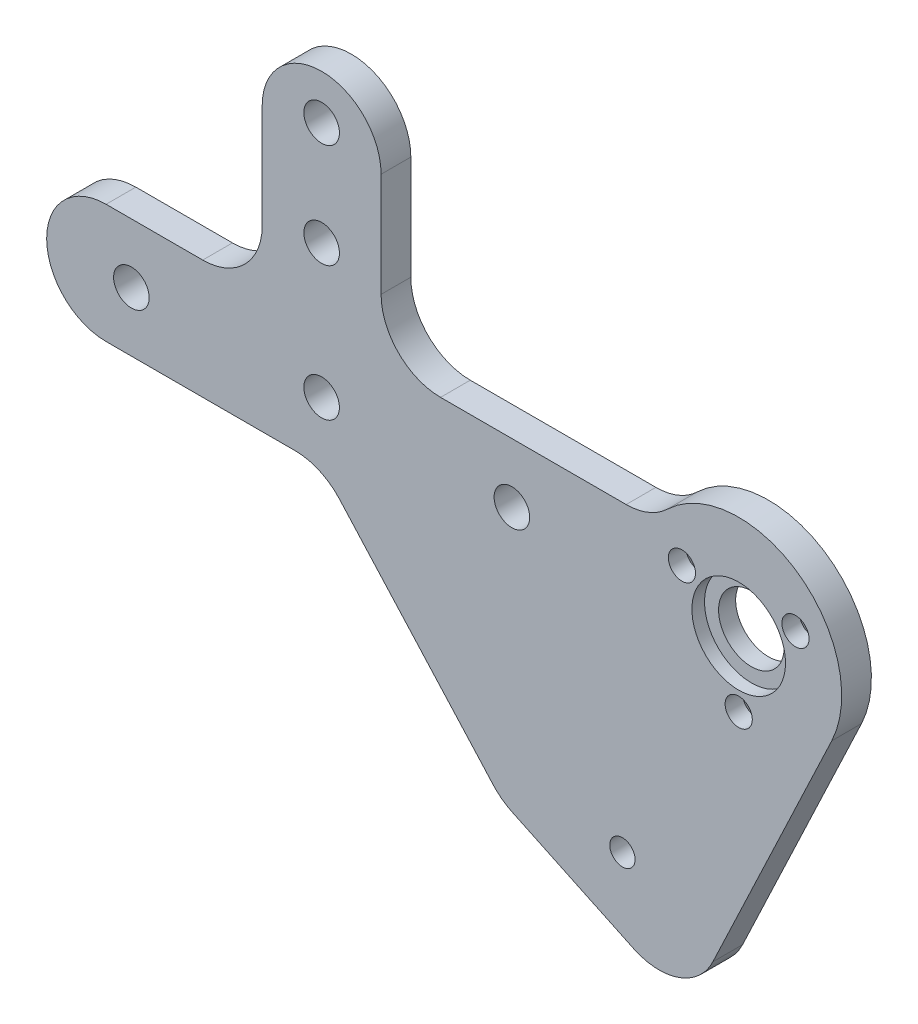
SolidWorks part; units mm, degrees
material "6061 Alloy"
ref_plane "Front Plane" through (0, 0, 0) normal (0, 0, 1) x (1, 0, 0)
ref_plane "Top Plane" through (0, 0, 0) normal (0, 1, 0) x (1, 0, 0)
ref_plane "Right Plane" through (0, 0, 0) normal (1, 0, 0) x (0, 0, -1)
sketch "Sketch1" plane through (0, 0, 0) normal (0, 0, 1) x (1, 0, 0)
  line L0 (0, 0) -> (0, 87.4403) construction
  line L1 (0, 0) -> (31.5741, 100.1403) construction
  line L2 (0, 0) -> (-31.5741, 100.1403) construction
  line L3 (-29.3687, 87.4403) -> (-29.3688, 100.1403)
  line L4 (29.3687, 100.1403) -> (35.4318, 100.1403)
  line L5 (31.5741, 100.1403) -> (-31.5741, 100.1403) construction
  line L6 (29.3687, 100.1403) -> (-29.3688, 100.1403)
  line L7 (0, 0) -> (38.5474, 81.3271) construction
  line L10 (-29.3687, 87.4403) -> (29.3687, 87.4403)
  line L12 (54.4836, 89.2666) -> (39.0647, 56.7358)
  line L13 (34.6037, 98.6893) -> (19.1847, 66.1585)
  line L14 (39.0647, 56.7358) -> (19.1847, 66.1585)
  line L17 (19.1847, 66.1585) -> (0, 87.4403)
  line L19 (0, 100.1403) -> (0, 123.9528) construction
  line L21 (6.35, 117.6028) -> (6.35, 100.1403)
  line L22 (-6.35, 117.6028) -> (-6.35, 100.1403)
  circle A0 centre (0, 0) radius 90 construction
  circle A1 centre (0, 0) radius 105 construction
  arc A2 (54.4836, 89.2666) -> (34.6037, 98.6893) centre (44.5437, 93.978) ccw
  circle A4 centre (44.5437, 93.978) radius 5
  circle A6 centre (0, 117.6028) radius 6.35
  circle A7 centre (44.5437, 93.978) radius 3.5
  point P14 (0, 100.1403)
  dimension "D1" = 17.5
  dimension "D3" = 25.36
  dimension "D6" = 180
  dimension "D4" = 23.8125
  dimension "D7" = 210
  dimension "D8" = 12.7
  dimension "D9" = 22
  dimension "D10" = 10
  dimension "D11" = 7
  dimension "D2" = 17.5
  dimension "D5" = 36
  dimension "D12" = 11
  dimension "D13" = 14
  dimension "D14" = 58.7375
  dimension "D15" = 12.7
extrude "Body" add sketch "Sketch1" along normal blind 3.175 contours A6 | A6 L22 A1 L21 | A1 A0 | L13 A1 A0 | A4 A1 L13 A0 L12 | L12 A0 L13 L14 | A4 A1 L12 A2 L13 | A7 A1 A4 | A7 A1 A4 | L13 A0 L17 | L3 L10 L6 region at (1.4838, 93.8941, 0) region at (16.1522, 80.3464, 0) region at (0, 106.4584, 0) region at (38.2064, 80.6077, 0) region at (0, 117.6028, 0) region at (39.6851, 93.978, 0)
hole_wizard "#6 Gimbal Clearance Hole" positions "3DSketch2" profile "Sketch3" hole size "#6" standard "Ansi Inch"
sketch3d "3DSketch2"
  line L1 (0, 0, 0) -> (0, 100.1403, 0) construction
  line L4 (0, 100.1403, 0) -> (0, 123.9528, 0) construction
  line L5 (6.35, 108.0778, 0) -> (-6.35, 108.0778, 0) construction
  line L6 (6.35, 119.1903, 0) -> (-6.35, 119.1903, 0) construction
  line L9 (-6.35, 117.6028, 0) -> (-6.35, 100.1403, 0) construction
  line L10 (6.35, 117.6028, 0) -> (6.35, 100.1403, 0) construction
  line L11 (20.8909, 100.1403, 0) -> (-17.8594, 100.1403, 0) construction
  line L13 (-6.35, 100.1403, 0) -> (-29.3688, 100.1403, 0) construction
  line L14 (6.35, 100.1403, 0) -> (35.4318, 100.1403, 0) construction
  arc A4 (6.35, 117.6028, 0) -> (-6.35, 117.6028, 0) centre (0, 117.6028, 0) ccw construction
  point P6 (0, 108.0778, 0)
  point P8 (0, 119.1903, 0)
  point P66 (0, 117.6028, 6.35)
  dimension "D1" = 7.9375
  dimension "D2" = 11.1125
sketch "Sketch3" plane through (0, 108.0778, 0) normal (1, 0, 0) x (0, 1, 0)
  line L0 (0, 0) -> (0, 13.1408)
  line L1 (0, 13.1408) -> (1.8986, 12)
  line L2 (1.8986, 12) -> (1.8986, 0)
  line L5 (1.8986, 0) -> (0, 0)
  line L10 (0, 13.1408) -> (-1.8986, 12) construction
  line L11 (0, -6.35) -> (0, 107.95) construction
  dimension "Hole Dia." = 3.7973
  dimension "Hole Depth" = 12
  dimension "Drill Angle" = 118
hole_wizard "CSK for M2.5 Flat Head Machine Screw" positions "3DSketch3" profile "Sketch4" countersink size "M2.5" standard "Ansi Metric" end condition through all
sketch3d "3DSketch3"
  line L8 (44.5437, 93.978, 3.175) -> (44.5437, 93.978, 0) construction
  line L9 (44.5437, 93.978, 3.175) -> (44.5437, 93.978, 0) construction
  line L21 (44.5437, 93.978, 0) -> (44.5437, 82.978, 0) construction
  line L22 (44.5437, 93.978, 0) -> (35.0174, 99.478, 0) construction
  line L23 (44.5437, 93.978, 0) -> (54.0699, 99.478, 0) construction
  circle A7 centre (44.5437, 93.978, 0) radius 7
  circle A8 centre (44.5437, 93.978, 0) radius 11
  point P0 (50.6058, 97.478, 0)
  point P50 (44.5437, 93.978, 7)
  point P67 (44.5437, 93.978, 11)
  point P134 (44.5437, 86.978, 0)
  point P136 (38.4815, 97.478, 0)
  dimension "D1" = 14
  dimension "D2" = 120
  dimension "D4" = 22
  dimension "D3" = 120
sketch "Sketch4" plane through (50.6058, 97.478, 0) normal (1, 0, 0) x (0, 1, 0)
  line L0 (0, 0) -> (0, 3.175)
  line L1 (0, 3.175) -> (1.45, 3.175)
  line L2 (1.45, 3.175) -> (1.45, 1.3)
  line L3 (1.45, 1.3) -> (2.75, 0)
  line L5 (2.75, 0) -> (0, 0)
  line L6 (-1.45, 1.3) -> (-2.75, 0) construction
  line L11 (0, -6.35) -> (0, 107.95) construction
  dimension "Thru Hole Dia." = 2.9
  dimension "Thru Hole Depth" = 3.175
  dimension "Near C'Sink Dia." = 5.5
  dimension "Near C'Sink Angle" = 90
hole_wizard "#6 Circular Clearance Holes" positions "3DSketch4" profile "Sketch5" hole size "#6" standard "Ansi Inch"
sketch3d "3DSketch4"
  line L1 (0, 0, 0) -> (0, 100.1403, 0) construction
  line L4 (20.8909, 100.1403, 0) -> (-17.8594, 100.1403, 0) construction
  line L6 (-6.35, 100.1403, 0) -> (-29.3688, 100.1403, 0) construction
  line L7 (0, 100.1403, 0) -> (0, 93.7903, 0) construction
  line L9 (20.32, 93.7903, 0) -> (-20.32, 93.7903, 0) construction
  line L10 (6.35, 100.1403, 0) -> (35.4318, 100.1403, 0) construction
  point P0 (-20.32, 93.7903, 0)
  point P2 (0, 93.7903, 0)
  point P4 (20.32, 93.7903, 0)
  dimension "D1" = 40.64
  dimension "D2" = 6.35
sketch "Sketch5" plane through (-20.32, 93.7903, 0) normal (1, 0, 0) x (0, 1, 0)
  line L0 (0, 0) -> (0, 13.1408)
  line L1 (0, 13.1408) -> (1.8986, 12)
  line L2 (1.8986, 12) -> (1.8986, 0)
  line L5 (1.8986, 0) -> (0, 0)
  line L10 (0, 13.1408) -> (-1.8987, 12) construction
  line L11 (0, -6.35) -> (0, 107.95) construction
  dimension "Hole Dia." = 3.7973
  dimension "Hole Depth" = 12
  dimension "Drill Angle" = 118
extrude "Motor Collar Relief" cut sketch "Sketch1<3>" along normal through all from offset 1.8263 contours A7 A1 A4 | A7 A1 A4 region at (39.6851, 93.978, 0)
sketch "Sketch1<3>" plane through (0, 0, 0) normal (0, 0, 1) x (1, 0, 0) same geometry as "Sketch1"
hole_wizard "#6-32 Tapped Hole" positions "3DSketch5" profile "Sketch6" tap size "#6-32" standard "Ansi Inch"
sketch3d "3DSketch5"
  line L0 (44.5437, 93.978, 0) -> (32.1228, 67.7726, 0) construction
  line L1 (44.5437, 93.978, 1.8263) -> (44.5437, 93.978, 0) construction
  line L3 (54.4836, 89.2666, 0) -> (39.0647, 56.7358, 0) construction
  point P0 (32.1228, 67.7726, 0)
  dimension "D1" = 29
sketch "Sketch6" plane through (32.1228, 67.7726, 0) normal (1, 0, 0) x (0, 1, 0)
  line L0 (0, 0) -> (0, 181.2543)
  line L1 (0, 181.2543) -> (1.3525, 180.4416)
  line L2 (1.3525, 180.4416) -> (1.3525, 0)
  line L5 (1.3525, 0) -> (0, 0)
  line L10 (0, 181.2543) -> (-1.3526, 180.4416) construction
  line L11 (0, -6.35) -> (0, 107.95) construction
  dimension "Tap Drill Dia." = 2.7051
  dimension "Tap Drill Depth" = 180.4416
  dimension "Drill Angle" = 118
cosmetic thread "Hole Thread1" parameters "D1"=3.175, "D2"=3.5052
fillet "Fillet1" radius 6.35 8 edges at (39.0647, 56.7358, 1.5875) (19.1847, 66.1585, 1.5875) (0, 87.4403, 1.5875) (-29.3687, 87.4403, 1.5875) (-29.3688, 100.1403, 1.5875) (-6.35, 100.1403, 1.5875) (35.4318, 100.1403, 1.5875) (6.35, 100.1403, 1.5875)
